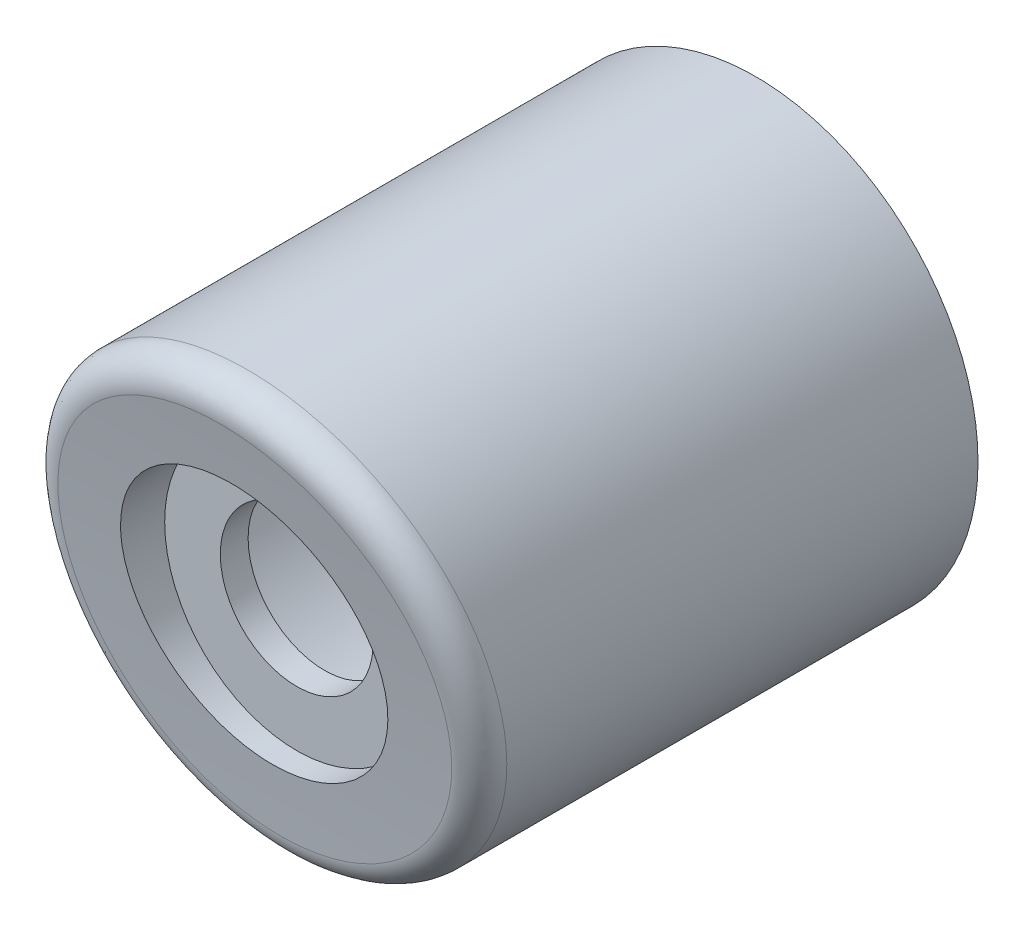
SolidWorks part; units mm, degrees
material "PA Type 6"
ref_plane "Front Plane" through (0, 0, 0) normal (0, 0, 1) x (1, 0, 0)
ref_plane "Top Plane" through (0, 0, 0) normal (0, 1, 0) x (1, 0, 0)
ref_plane "Right Plane" through (0, 0, 0) normal (1, 0, 0) x (0, 0, -1)
sketch "Sketch1" plane through (0, 0, 0) normal (0, 0, 1) x (1, 0, 0)
  line L1 (4, -14) -> (-4, -14)
  line L2 (4, -14) -> (4, -18)
  line L3 (4, -18) -> (-4, -18)
  line L4 (-4, -14) -> (-4, -18)
  line L5 (4, -14) -> (-4, -18) construction
  line L6 (4, -18) -> (-4, -14) construction
  circle A0 centre (0, 0) radius 16
  circle A1 centre (0, 0) radius 14
  point P3 (0, -16)
  dimension "D1" = 32
  dimension "D4" = 28
  dimension "D2" = 4
  dimension "D3" = 8
extrude "Boss-Extrude1" add sketch "Sketch1" along normal blind 27 contours A1 L2 A0 L4 | A1 L4 A0 L2 region at (0, -14.9221, 0) region at (2, -13.9551, 0)
extrude "Boss-Extrude2" add sketch "Sketch1<3>" along normal blind 22 contours A0 L4 L3 L2 region at (0, -16.9106, 0)
sketch "Sketch1<3>" plane through (0, 0, 0) normal (0, 0, 1) x (1, 0, 0) same geometry as "Sketch1"
fillet "Fillet1" radius 3 1 edges at (0, -16, 22)
ref_plane "Plane1" through (0, 0, 27) normal (0, 0, -1) x (-1, 0, 0)
sketch "Sketch3" plane through (0, 0, 27) normal (0, 0, -1) x (-1, 0, 0)
  circle A0 centre (0, 0) radius 5.5
  circle A1 centre (0, 0) radius 9.5
  circle A2 centre (0, 0) radius 16
  circle A3 centre (0, 0) radius 15.25
  dimension "D1" = 11
  dimension "D2" = 19
  dimension "D3" = 32
  dimension "D4" = 30.5
extrude "Boss-Extrude7" add sketch "Sketch3<5>" against normal blind 12 contours A2 A3 region at (15.5475, 0, 27)
sketch "Sketch3<5>" plane through (0, 0, 27) normal (0, 0, -1) x (-1, 0, 0) same geometry as "Sketch3"
extrude "Boss-Extrude8" add sketch "Sketch3<6>" against normal blind 8 from offset 4 contours A3 A1 region at (14.8187, 0, 27) offset against normal yes
sketch "Sketch3<6>" plane through (0, 0, 27) normal (0, 0, -1) x (-1, 0, 0) same geometry as "Sketch3"
extrude "Boss-Extrude9" add sketch "Sketch3" against normal blind 2 from offset 4 contours A1 A0 region at (9.2313, 0, 27) offset against normal yes
sketch "Sketch5" plane through (0, 0, 0) normal (1, 0, 0) x (0, 0, -1)
  line L0 (-39, -16) -> (-24.8284, -16) construction
  line L1 (-39, -16) -> (-34, -16)
  line L2 (-39, 16) -> (-39, -16) construction
  line L3 (-39, 16) -> (-39, -16)
  line L4 (-27, -17.6) -> (-27, 17.6) construction
  arc A0 (-34, -16) -> (-39, 16) centre (-332.4715, -46.2455) ccw
  dimension "D2" = 300
  dimension "D1" = 7
extrude "Cut-Extrude2" cut sketch "Sketch5" against normal up to next and the other way up to next
fillet "Fillet3" radius 2 1 edges at (0, -16, 34)
